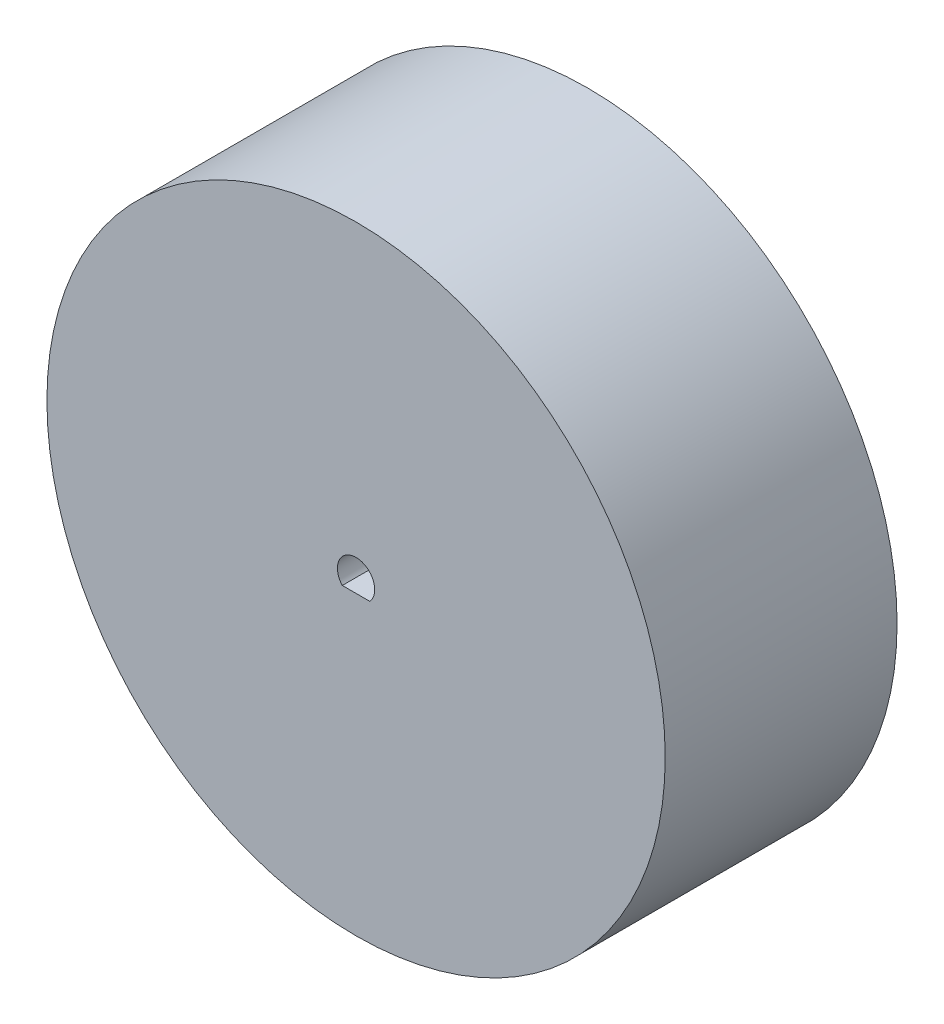
SolidWorks part; units mm, degrees
ref_plane "Front Plane" through (0, 0, 0) normal (0, 0, 1) x (1, 0, 0)
ref_plane "Top Plane" through (0, 0, 0) normal (0, 1, 0) x (1, 0, 0)
ref_plane "Right Plane" through (0, 0, 0) normal (1, 0, 0) x (0, 0, -1)
sketch "Sketch1" plane through (0, 0, 0) normal (0, 0, 1) x (1, 0, 0)
  line L0 (-1.118, -1) -> (-0.8307, -1) construction
  line L1 (-0.8307, -1) -> (0.8307, -1) construction
  line L2 (0.8307, -1) -> (1.118, -1) construction
  line L3 (-1.118, -1) -> (-0.8307, -1) construction
  line L4 (-0.8307, -1) -> (0.8307, -1) construction
  line L5 (0.8307, -1) -> (1.118, -1) construction
  line L6 (-1.1314, -1.03) -> (-0.8307, -1.03)
  line L7 (-0.8307, -1.03) -> (0.8307, -1.03)
  line L8 (0.8307, -1.03) -> (1.1314, -1.03)
  circle A0 centre (0, 0) radius 25.4
  arc A1 (-1.5, 0) -> (-1.118, -1) centre (0, 0) ccw construction
  arc A2 (1.118, -1) -> (1.5, 0) centre (0, 0) ccw construction
  arc A3 (1.5, 0) -> (-1.5, 0) centre (0, 0) ccw construction
  arc A4 (-1.5, 0) -> (-1.118, -1) centre (0, 0) ccw construction
  arc A5 (1.118, -1) -> (1.5, 0) centre (0, 0) ccw construction
  arc A6 (1.5, 0) -> (-1.5, 0) centre (0, 0) ccw construction
  arc A7 (1.53, 0) -> (-1.53, 0) centre (0, 0) ccw
  arc A8 (-1.53, 0) -> (-1.1314, -1.03) centre (0, 0) ccw
  arc A9 (1.1314, -1.03) -> (1.53, 0) centre (0, 0) ccw
  dimension "D1" = 50.8
  dimension "D2" = 0.03
extrude "Boss-Extrude1" add sketch "Sketch1" against normal mid plane 19.05
